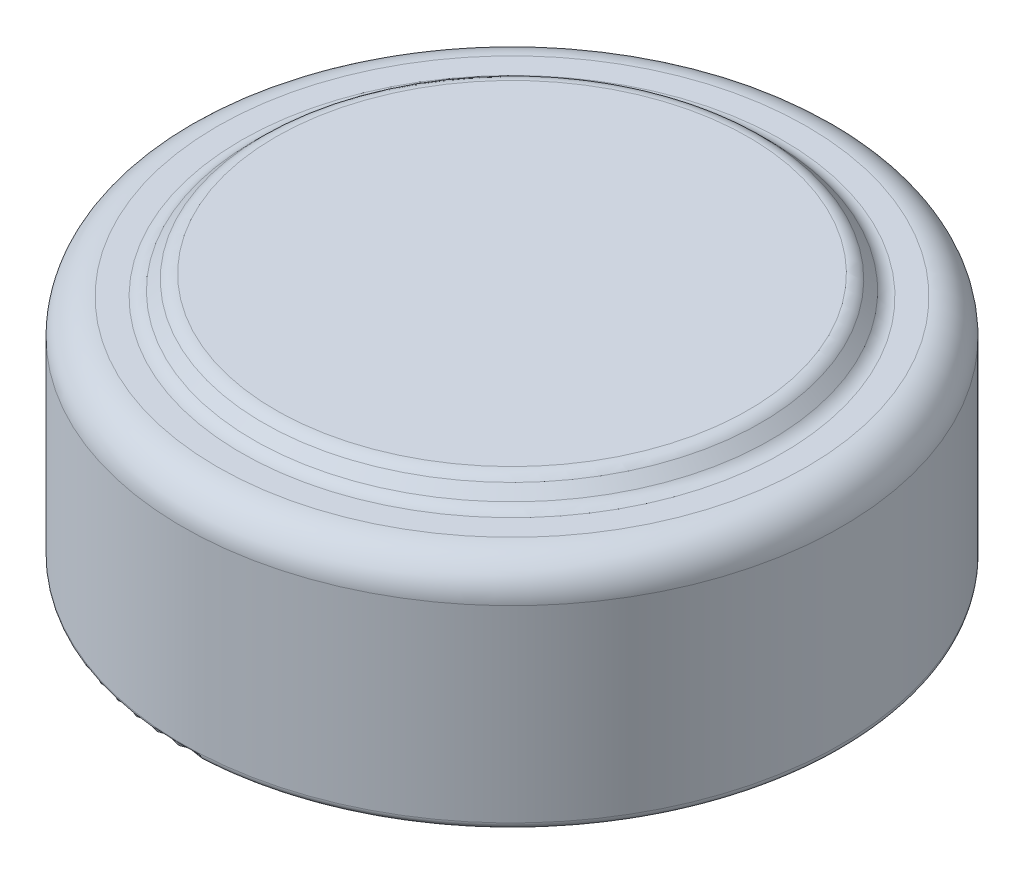
SolidWorks part; units mm, degrees
ref_plane "Front Plane" through (0, 0, 0) normal (0, 0, 1) x (1, 0, 0)
ref_plane "Top Plane" through (0, 0, 0) normal (0, 1, 0) x (1, 0, 0)
ref_plane "Right Plane" through (0, 0, 0) normal (1, 0, 0) x (0, 0, -1)
sketch "Sketch1" plane through (0, 0, 0) normal (0, 0, 1) x (1, 0, 0)
  line L0 (0, 0) -> (-4.65, 0)
  line L1 (-4.75, 0.1) -> (-4.75, 2.812)
  line L2 (-3.4084, 3.6) -> (0, 3.6)
  line L3 (0, 3.6) -> (0, 0)
  line L4 (-3.5852, 3.5268) -> (-3.7268, 3.3852)
  line L7 (-4.25, 3.312) -> (-3.9036, 3.312)
  arc A0 (-4.75, 2.812) -> (-4.25, 3.312) centre (-4.25, 2.812) cw
  arc A1 (-3.9036, 3.312) -> (-3.7268, 3.3852) centre (-3.9036, 3.562) ccw
  arc A2 (-3.4084, 3.6) -> (-3.5852, 3.5268) centre (-3.4084, 3.35) ccw
  arc A3 (-4.65, 0) -> (-4.75, 0.1) centre (-4.65, 0.1) cw
  point P9 (-4.75, 3.312)
  point P12 (-3.8, 3.312)
  point P14 (-3.512, 3.6)
  point P17 (-4.75, 0)
  dimension "D6" = 0.5
  dimension "D7" = 0.25
  dimension "D8" = 0.1
  dimension "D1" = 4.75
  dimension "D2" = 3.6
  dimension "D3" = 3.8
  dimension "D4" = 3.312
  dimension "D5" = 45
revolve "Revolve1" add sketch "Sketch1" angle 360 about L3
sketch "Sketch2" plane through (0, 0, 0) normal (0, -1, 0) x (1, 0, 0)
  line L0 (0.25, 0.25) -> (2, 0.25)
  line L1 (-0.25, 2) -> (0.25, 2)
  line L2 (-0.25, 2) -> (-0.25, 0.25)
  line L3 (-0.25, -2) -> (0.25, -2)
  line L4 (0.25, 2) -> (0.25, 0.25)
  line L5 (-2, 0.25) -> (-0.25, 0.25)
  line L6 (-2, 0.25) -> (-2, -0.25)
  line L7 (-2, -0.25) -> (-0.25, -0.25)
  line L8 (2, 0.25) -> (2, -0.25)
  line L9 (0.25, -0.25) -> (2, -0.25)
  line L10 (0.25, -0.25) -> (0.25, -2)
  line L11 (-0.25, -0.25) -> (-0.25, -2)
  circle A0 centre (0, 0) radius 3.25 construction
  text T0 "                          SR45" font "Century Gothic" height 1
  dimension "D1" = 6.5
  dimension "D2" = 0.5
  dimension "D3" = 0.5
  dimension "D4" = 0.25
  dimension "D5" = 0.25
  dimension "D6" = 4
  dimension "D7" = 2
  dimension "D8" = 2
  dimension "D9" = 4
wrap "Wrap1" sketch "Sketch2" wrap type scribe source sketch "Sketch2" face at (-4.65, 0, 0)
